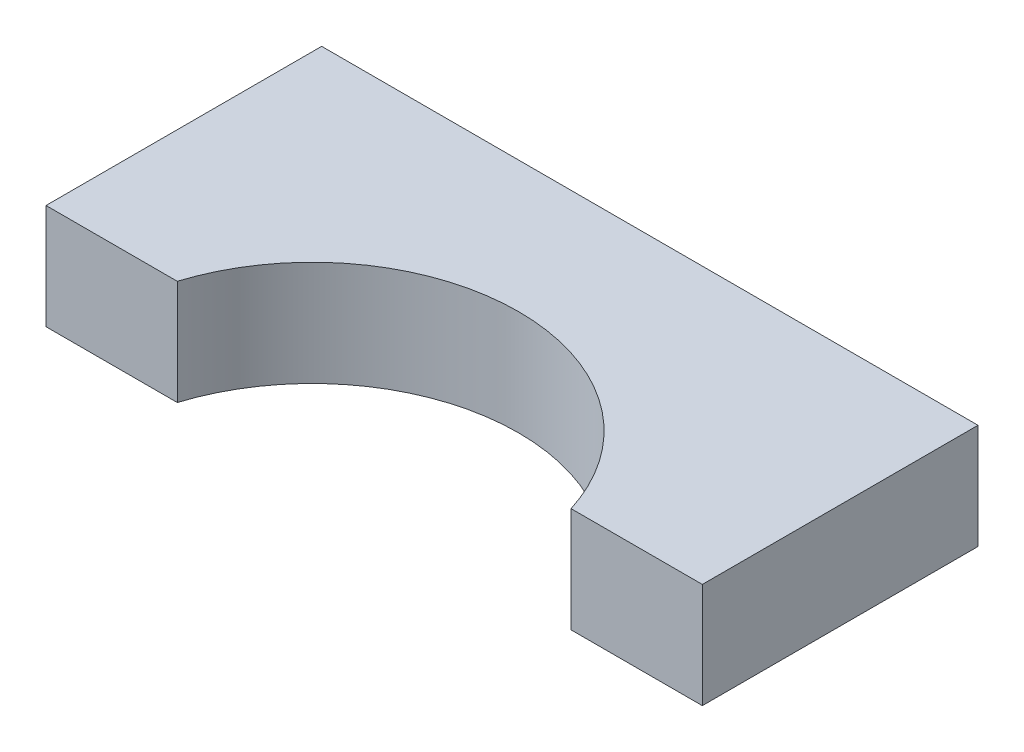
SolidWorks part; units mm, degrees
material "PLA"
ref_plane "Front" through (0, 0, 0) normal (0, 0, 1) x (1, 0, 0)
ref_plane "Top" through (0, 0, 0) normal (0, 1, 0) x (1, 0, 0)
ref_plane "Right" through (0, 0, 0) normal (1, 0, 0) x (0, 0, -1)
sketch "Sketch2" plane through (0, 0, 0) normal (0, 1, 0) x (1, 0, 0)
  line L0 (19.05, -13.97) -> (31.75, -13.97)
  line L1 (-31.75, 12.7) -> (31.75, 12.7)
  line L2 (-31.75, 12.7) -> (-31.75, -13.97)
  line L3 (-31.75, -13.97) -> (-19.05, -13.97)
  line L4 (31.75, 12.7) -> (31.75, -13.97)
  arc A2 (-19.05, -13.97) -> (19.05, -13.97) centre (0, -19.9736) cw
  point P0 (0, 0)
  dimension "D1" = 63.5
  dimension "D2" = 26.67
  dimension "D3" = 12.7
  dimension "D4" = 12.7
extrude "Boss-Extrude1" add sketch "Sketch2" against normal blind 10.16
